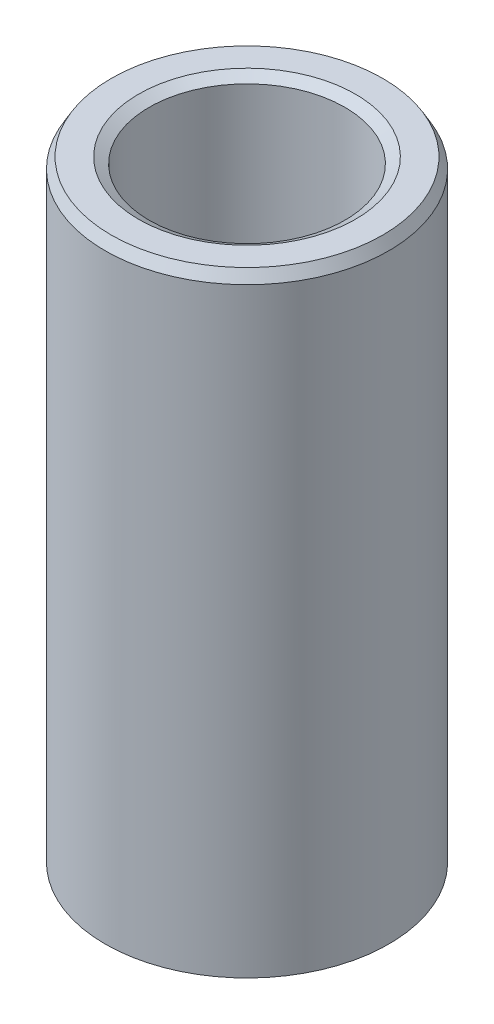
SolidWorks part; units mm, degrees
ref_plane "Front Plane" through (0, 0, 0) normal (0, 0, 1) x (1, 0, 0)
ref_plane "Top Plane" through (0, 0, 0) normal (0, 1, 0) x (1, 0, 0)
ref_plane "Right Plane" through (0, 0, 0) normal (1, 0, 0) x (0, 0, -1)
sketch "Sketch1" plane through (0, 0, 0) normal (0, 1, 0) x (1, 0, 0)
  circle A0 centre (0, 0) radius 40
  dimension "SLEEVE_OD" = 80
extrude "Boss-Extrude1" add sketch "Sketch1" along normal blind 174.0117
sketch "Sketch2" plane through (0, 0, 0) normal (0, 1, 0) x (1, 0, 0)
  circle A0 centre (0, 0) radius 27.6057
  dimension "BORE_D" = 55.2114
extrude "Cut-Extrude1" cut sketch "Sketch2" along normal through all
chamfer "Chamfer1" distance 2.9776 angle 30 4 edges at (0, 174.0117, 27.6057) (0, 0, 27.6057) (0, 0, 40) (0, 174.0117, 40) first distance on face at (0, 174.0117, 27.6057) first distance on face at (0, 0, 27.6057) first distance on face at (0, 174.0117, 40)
